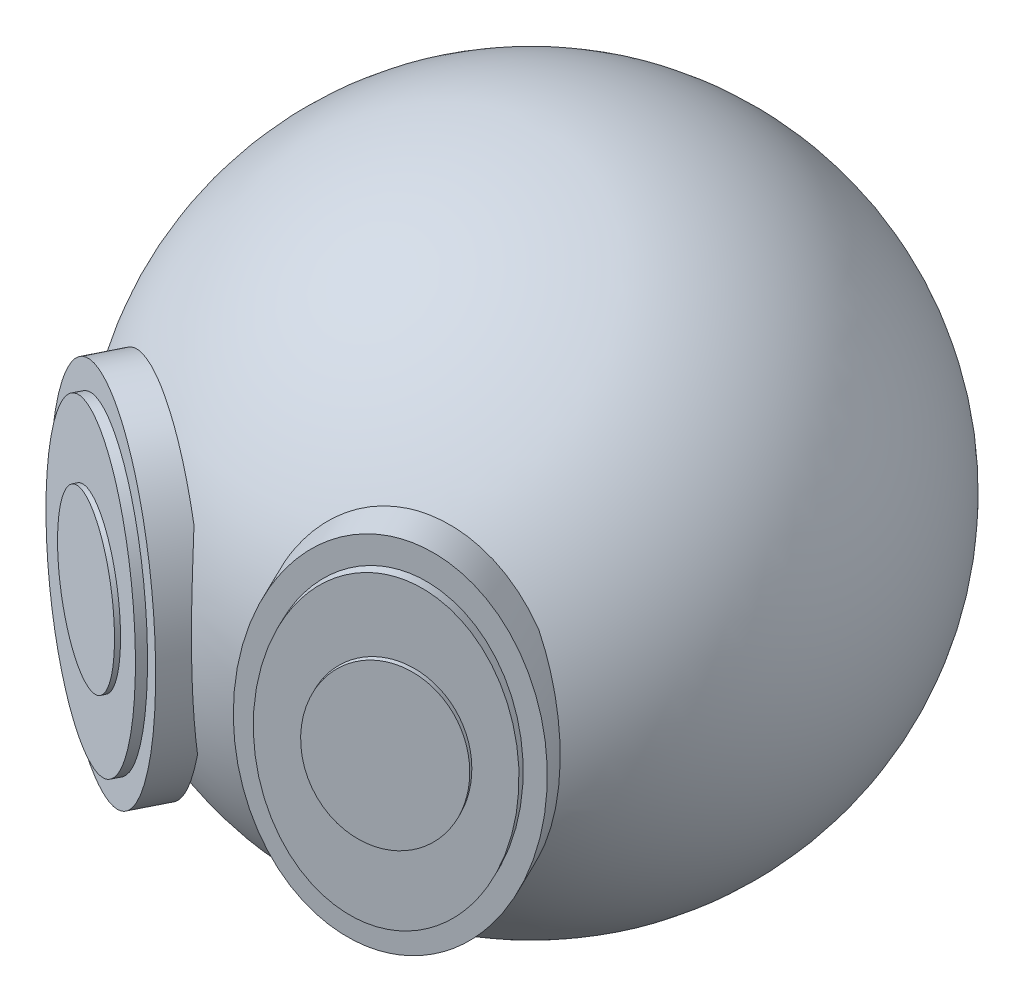
SolidWorks part; units mm, degrees
ref_plane "Alzado" through (0, 0, 0) normal (0, 0, 1) x (1, 0, 0)
ref_plane "Planta" through (0, 0, 0) normal (0, 1, 0) x (1, 0, 0)
ref_plane "Vista lateral" through (0, 0, 0) normal (1, 0, 0) x (0, 0, -1)
sketch "Croquis1" plane through (0, 0, 0) normal (0, 0, 1) x (1, 0, 0)
  line L0 (-20.6427, 127.9829) -> (-20.6427, 57.9829)
  arc A0 (-20.6427, 127.9829) -> (-20.6427, 57.9829) centre (-20.6427, 92.9829) ccw
revolve "Revolución1" add sketch "Croquis1" angle 360 about L0
ref_plane "Plano1" through (0, 94, 0) normal (0, 1, 0) x (1, 0, 0)
sketch "Croquis2" plane through (0, 94, 0) normal (0, 1, 0) x (1, 0, 0)
  line L0 (-20.6427, -35) -> (14.3573, -35)
  line L1 (-11.2235, -33.6317) -> (0.4617, -27.9347)
  line L2 (-30.2931, -33.6317) -> (-41.748, -27.9347)
  line L3 (-36.3557, -30.6165) -> (-36.1651, -30.2331)
  line L4 (-36.1651, -30.2331) -> (-35.6125, -30.5079)
  line L5 (-35.6125, -30.5079) -> (-35.8031, -30.8913)
  line L6 (-5.6027, -30.8913) -> (-5.7367, -30.6165)
  line L7 (-5.7367, -30.6165) -> (-5.2458, -30.3772)
  line L8 (-5.2458, -30.3772) -> (-5.1118, -30.652)
  line L9 (-36.1651, -30.2331) -> (-35.6377, -30.4954)
  line L10 (-36.1651, -30.2331) -> (-36.3575, -30.6201)
  line L11 (-35.6377, -30.4954) -> (-35.8302, -30.8824)
  line L12 (-36.3575, -30.6201) -> (-35.8302, -30.8824)
  line L13 (-5.7367, -30.6165) -> (-5.2458, -30.3772)
  line L14 (-5.7367, -30.6165) -> (-5.6027, -30.8913)
  line L15 (-5.2458, -30.3772) -> (-5.1118, -30.652)
  line L16 (-5.6027, -30.8913) -> (-5.1118, -30.652)
  circle A0 centre (-20.6427, 0) radius 35 construction
extrude "Saliente-Extruir1" add sketch "Croquis2" along normal blind 8 contours L8 L7 L6 L1 | L11 L4 L3 L2 region at (-5.4242, 94, 30.6342) region at (-35.9967, 94, 30.5559)
sketch "Croquis7" plane through (-19.4165, 0, 39.041) normal (-0.4453, 0, 0.8954) x (0.8954, 0, 0.4453)
  line L0 (-18.3295, 99.3779) -> (-18.3295, 92.3779)
  ellipse E0 centre (-18.3295, 92.3779) end of major axis (-18.3295, 112.3779) minor radius 13
  line M2 (-18.9185, 102) -> (-18.9185, 99.365)
  arc M3 (-18.9185, 99.365) -> (-18.3295, 99.3779) centre (-18.483, 92.9829) cw
  line M4 (-18.3295, 99.3779) -> (-18.3295, 102)
  line M5 (-18.3295, 102) -> (-18.9185, 102)
extrude "Saliente-Extruir9" add sketch "Croquis7" along normal blind 1 and the other way blind 3 contours M2 M5 M4 M3 region at (-35.8279, 92.3622, 30.879)
sketch "Croquis8" plane through (11.0924, 0, 22.7518) normal (0.4382, 0, 0.8989) x (0.8989, 0, -0.4382)
  ellipse E0 centre (-18.0274, 92.6347) end of major axis (-18.0274, 112.6347) minor radius 13
  arc M2 (-18.5736, 99.6555) -> (-18.0274, 99.6347) centre (-18.555, 92.9829) cw
  line M3 (-18.0274, 99.6347) -> (-18.0274, 102)
  line M4 (-18.0274, 102) -> (-18.5736, 102)
  line M5 (-18.5736, 102) -> (-18.5736, 99.6555)
extrude "Saliente-Extruir10" add sketch "Croquis8" along normal blind 1 and the other way blind 3 contours M2 M5 M4 M3 region at (-5.1114, 92.6218, 30.6518)
sketch "Croquis9" plane through (-19.8618, 0, 39.9364) normal (-0.4453, 0, 0.8954) x (0.8954, 0, 0.4453)
  ellipse E0 centre (-18.3295, 92.3779) end of major axis (-18.3295, 109.3779) minor radius 11
extrude "Saliente-Extruir11" add sketch "Croquis9" along normal blind 1
sketch "Croquis10" plane through (11.5306, 0, 23.6507) normal (0.4382, 0, 0.8989) x (0.8989, 0, -0.4382)
  ellipse E0 centre (-18.0274, 92.6347) end of major axis (-18.0274, 109.6347) minor radius 11
extrude "Saliente-Extruir12" add sketch "Croquis10" along normal blind 1
sketch "Croquis13" plane through (0, 0, 0) normal (0, 0, 1) x (1, 0, 0)
  line L0 (-48.3587, 86.8669) -> (-48.3587, 102.1243)
  line L1 (-38.2549, 111.1297) -> (-32.0123, 111.1297)
  line L2 (7.5821, 104.7842) -> (7.5821, 88.5351)
  line L3 (-8.4165, 111.1297) -> (0, 111.1297)
  circle A0 centre (-20.6427, 92.9829) radius 35 construction
  arc A1 (-8.4165, 111.1297) -> (-13.0159, 108.4768) centre (-8.4165, 105.8162) ccw
  arc A2 (-32.0123, 111.1297) -> (-27.3717, 108.4042) centre (-32.0123, 105.8162) cw
  arc A3 (-2.3413, 63.1491) -> (-41.0607, 64.5558) centre (-20.6427, 92.9829) ccw
  spline S0 degree 2 poles (-48.3587, 102.1243) (-46.2401, 110.7807) (-38.2549, 111.1297) knots 0 0 0 1 1 1
  spline S1 degree 3 poles (-27.3717, 108.4042) (-25.0713, 104.2794) (-20.3196, 100.0168) (-15.5026, 104.1781) (-13.0159, 108.4768) knots 0.08245 0.08245 0.08245 0.08245 0.493757 0.919955 0.919955 0.919955 0.919955
  spline S2 degree 2 poles (0, 111.1297) (5.7057, 110.8942) (7.5821, 104.7842) knots 0 0 0 1 1 1
  spline S3 degree 2 poles (-48.3587, 86.8669) (-48.0383, 74.4426) (-41.0607, 64.5558) knots 0 0 0 1 1 1
  spline S4 degree 2 poles (7.5821, 88.5351) (6.9532, 74.164) (-2.3413, 63.1491) knots 0 0 0 1 1 1
  dimension "D1" = 5.3135
sketch "Croquis14" plane through (11.9689, 0, 24.5496) normal (0.4382, 0, 0.8989) x (0.8989, 0, -0.4382)
  ellipse E0 centre (-17.9349, 92.6347) end of major axis (-17.9349, 101.6347) minor radius 7
extrude "Saliente-Extruir13" add sketch "Croquis14" along normal blind 0.5
sketch "Croquis15" plane through (-20.3071, 0, 40.8318) normal (-0.4453, 0, 0.8954) x (0.8954, 0, 0.4453)
  ellipse E0 centre (-17.9879, 92.3779) end of major axis (-17.9879, 101.3779) minor radius 7
extrude "Saliente-Extruir14" add sketch "Croquis15" along normal blind 0.5
ref_plane "Plano2" through (0, 0, 23) normal (0, 0, 1) x (1, 0, 0)
sketch "Croquis16" plane through (0, 0, 23) normal (0, 0, 1) x (1, 0, 0)
  circle A0 centre (-20.6427, 92.9829) radius 35 construction
  ellipse E0 centre (-36.2737, 92.3779) end of major axis (-36.2737, 72.3779) minor radius 11.6399
  ellipse E1 centre (-4.2353, 92.6347) end of major axis (-4.6735, 72.6347) minor radius 11.2489
  spline S0 degree 3 poles (-14.3141, 110.9777) (-13.1691, 112.0199) (-8.9809, 114.8099) (-0.5111, 114.8794) (6.6175, 106.4617) (10.5292, 88.335) (3.0419, 73.5072) (-0.9486, 64.0495) knots 0.156037 0.156037 0.156037 0.156037 0.213314 0.343152 0.422167 0.606755 1 1 1 1
  spline S1 degree 3 poles (-27.8269, 111.0238) (-29.0007, 112.1069) (-33.9823, 115.3682) (-43.614, 112.6064) (-48.3526, 103.6685) (-51.5056, 87.2601) (-43.6239, 73.6528) (-40.3369, 64.0495) knots 0.16553 0.16553 0.16553 0.16553 0.224644 0.386416 0.461262 0.601754 1 1 1 1
  spline S2 degree 3 poles (-27.8269, 111.0238) (-27.031, 110.7934) (-21.7287, 100.2198) (-17.9159, 102.8356) (-17.125, 108.7397) (-14.3141, 110.9777) knots 0 0 0 0 0.34957 0.404577 1 1 1 1
  spline S3 degree 2 poles (-40.3369, 64.0495) (-20.6427, 51.9163) (-0.9486, 64.0495) knots 0 0 0 1 1 1
sketch "Croquis20" plane through (0, 0, 0) normal (0, 1, 0) x (1, 0, 0)
  line L1 (-60.876, -27.3625) -> (22.8216, -27.3625)
  line L2 (-60.876, -27.3625) -> (-60.876, 34.7953)
  line L3 (-60.876, 34.7953) -> (22.8216, 34.7953)
  line L4 (22.8216, -27.3625) -> (22.8216, 34.7953)
